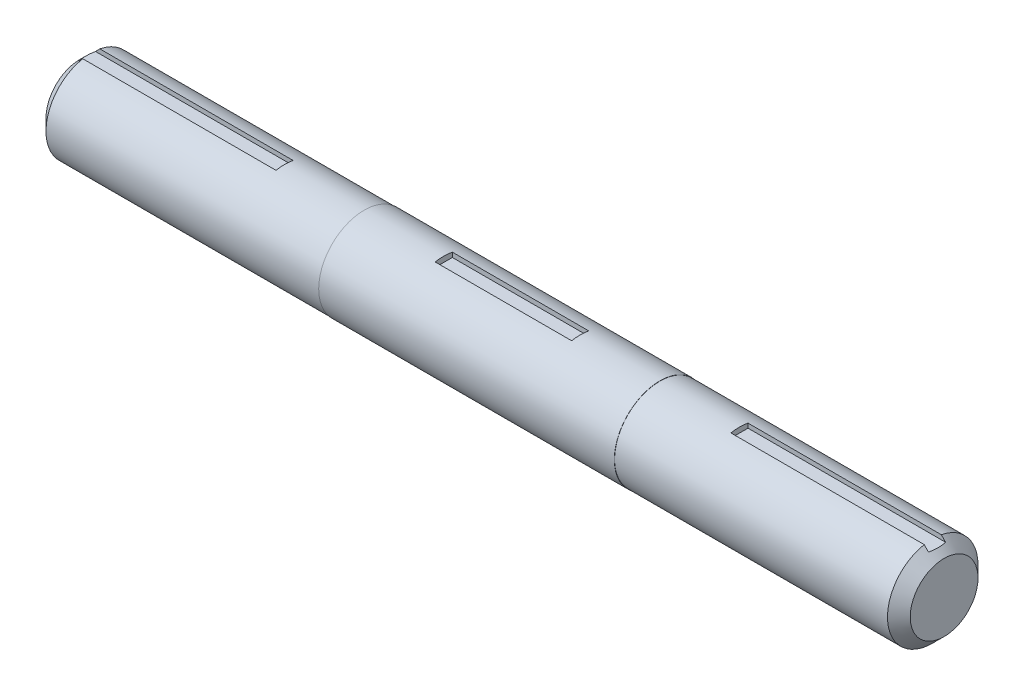
SolidWorks part; units mm, degrees
ref_plane "Front Plane" through (0, 0, 0) normal (0, 0, 1) x (1, 0, 0)
ref_plane "Top Plane" through (0, 0, 0) normal (0, 1, 0) x (1, 0, 0)
ref_plane "Right Plane" through (0, 0, 0) normal (1, 0, 0) x (0, 0, -1)
sketch "Sketch1" plane through (0, 0, 0) normal (1, 0, 0) x (0, 0, -1)
  circle A0 centre (0, 0) radius 12.6365
  dimension "D1" = 25.273
extrude "Boss-Extrude1" add sketch "Sketch1" against normal blind 79.375
sketch "Sketch2" plane through (-79.375, 0, 0) normal (-1, 0, 0) x (0, 0, 1)
  circle A0 centre (0, 0) radius 12.7
  dimension "D1" = 25.4
extrude "Boss-Extrude2" add sketch "Sketch2" along normal blind 82.55
sketch "Sketch3" plane through (-161.925, 0, 0) normal (-1, 0, 0) x (0, 0, 1)
  circle A0 centre (0, 0) radius 12.6365
  dimension "D1" = 25.273
extrude "Boss-Extrude3" add sketch "Sketch3" along normal blind 79.375
chamfer "Chamfer1" distance 3.175 angle 45 2 edges at (-241.3, 0, 12.6365) (0, 0, -12.6365)
sketch "Sketch4" plane through (0, 0, 0) normal (1, 0, 0) x (0, 0, -1)
  line L0 (-2.3876, 11.176) -> (2.3876, 11.176)
  line L1 (2.3876, 11.176) -> (2.3876, 12.4735)
  line L2 (-2.3876, 11.176) -> (-2.3876, 12.4735)
  line L3 (0, 0) -> (0, 12.6365) construction
  circle A0 centre (0, 0) radius 12.6365 construction
  circle A1 centre (0, 0) radius 12.7 construction
  arc A2 (-2.3876, 12.4735) -> (2.3876, 12.4735) centre (0, 0) cw
  point P3 (0, -12.6365)
  dimension "D1" = 4.7752
  dimension "D2" = 23.8125
extrude "Cut-Extrude1" cut sketch "Sketch4" against normal blind 57.15 contours A2 L2 L0 L1 region at (0, 11.902, 0)
extrude "Cut-Extrude2" cut sketch "Sketch4<2>" along normal blind 57.15 from surface contours A2 L2 L0 L1 region at (0, 11.902, 0) starting at face at (-241.3, 0, 9.4615)
sketch "Sketch4<2>" plane through (0, 0, 0) normal (1, 0, 0) x (0, 0, -1) same geometry as "Sketch4"
ref_plane "Plane1" through (-120.65, 0, 0) normal (1, 0, 0) x (0, 0, -1)
extrude "Cut-Extrude3" cut sketch "Sketch4<4>" against normal mid plane 38.1 from surface contours A2 L2 L0 L1 region at (0, 11.902, 0) starting at plane "Plane1"
sketch "Sketch4<4>" plane through (0, 0, 0) normal (1, 0, 0) x (0, 0, -1) same geometry as "Sketch4"
